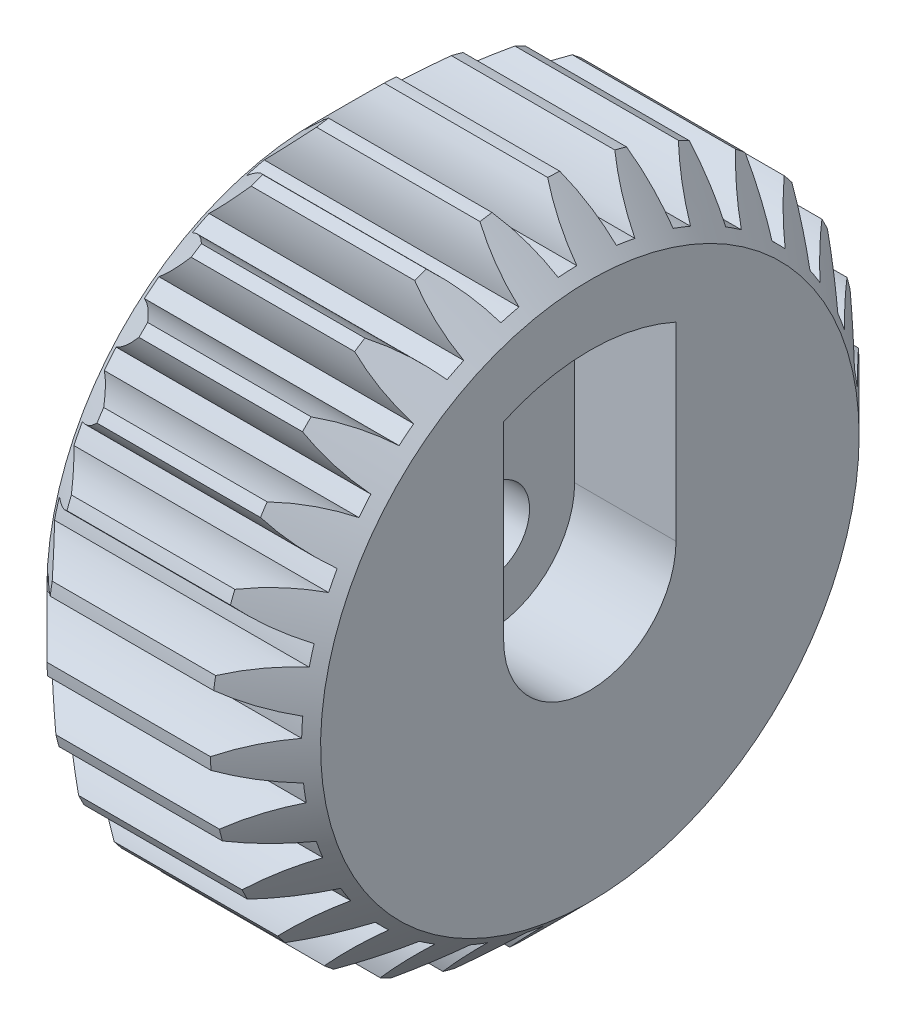
SolidWorks part; units mm, degrees
ref_plane "Plane1" through (0, 0, 0) normal (0, 0, 1) x (1, 0, 0)
ref_plane "Plane2" through (0, 0, 0) normal (0, 1, 0) x (1, 0, 0)
ref_plane "Plane3" through (0, 0, 0) normal (1, 0, 0) x (0, 0, -1)
sketch "HoldingSke" plane through (0, 0, 0) normal (0, 1, 0) x (1, 0, 0)
  line L0 (0, 0) -> (0.4698, -0.171)
  line L1 (-15, 0) -> (100, 0) construction
  line L2 (0, 0) -> (-2.1039, 2.3779)
  line L3 (0, 0) -> (-11.863, 4.5341)
  line L4 (0, 0) -> (8.1152, 2.9537)
  line L5 (0, 0) -> (-46.8476, -17.4728)
  line L6 (0, 0) -> (-39.7902, -26.8466)
  line L7 (-2.1039, 2.3779) -> (8.6589, 51.2074)
  line L8 (-76.2, 54.61) -> (-73.4, 54.61)
  line L9 (-71.009, 38.7566) -> (-53.1078, 45.2721)
  line L10 (-76.2, 71.12) -> (104.1128, 71.12)
  line L11 (0, 0) -> (-48, 0)
  line L12 (-76.2, 101.6) -> (-76.133, 101.6)
  line L13 (24.9733, 27.94) -> (52.9518, 28.4284)
  line L14 (24.9733, 27.94) -> (24.9743, 27.94)
  line L15 (24.9733, 27.94) -> (100.4006, 29.5858)
  line L16 (-63.627, -2) -> (-12.827, -2)
  circle A0 centre (0, 0) radius 10
  circle A1 centre (0, 0) radius 17.499
  circle A2 centre (0, 0) radius 37.5
  circle A3 centre (0, 0) radius 10
  dimension "MHD" = 34.998
  dimension "Hub_dia" = 75
  dimension "Bore" = 20
  dimension "MBD" = 20
  dimension "Num_teeth" = 20
  dimension "Pitch" = 0.5
  dimension "Overall_len" = 50
  dimension "Show_teeth" = 20
  dimension "Thickness" = 48
  dimension "OAL" = 50.0016
  dimension "T_dim" = 2.8
  dimension "Ap" = 20
  dimension "H" = 19.05
  dimension "Pitch_radius" = 180.3128
  dimension "Width" = 48
  dimension "Backlash" = 0.067
  dimension "Addendum_fac" = 1
  dimension "Dedendum_fac" = 1.25
  dimension "Clearance_fac" = 0.25
  dimension "Dedendum_add" = 0.001
  dimension "Module" = 2
sketch "BasProSke" plane through (0, 0, 0) normal (0, 1, 0) x (1, 0, 0)
  line L0 (-10, 0) -> (60, 0) construction
  line L1 (0, 0) -> (0, 22)
  line L2 (0, 0) -> (-31, 0)
  line L3 (-31, 0) -> (-31, 22)
  line L4 (-31, 22) -> (0, 22)
  dimension "Thickness" = 31
  dimension "Diameter" = 44
revolve "Base-Revolve" add sketch "BasProSke" angle 360 about L0
sketch "TooCutSke" plane through (0, 0, 0) normal (1, 0, 0) x (0, 0, -1)
  line L1 (0, 0) -> (0, 107) construction
  line L2 (0, 0) -> (-1.6864, 19.9288) construction
  line L3 (0, 0) -> (-6.2409, 39.4033) construction
  line L4 (-1.6864, 19.9288) -> (-3.1204, 19.7016) construction
  arc A0 (0.9862, 17.4712) -> (-0.9862, 17.4712) centre (0, 0) ccw
  arc A1 (2.9329, 21.8293) -> (-2.9329, 21.8293) centre (0, 0) ccw
  circle A2 centre (0, 0) radius 20 construction
  circle A3 centre (0, 0) radius 18.7939 construction
  arc A4 (-0.9862, 17.4712) -> (-2.9329, 21.8293) centre (-8.9313, 16.536) ccw
  arc A5 (2.9329, 21.8293) -> (0.9862, 17.4712) centre (8.9313, 16.536) ccw
  dimension "Root_dia" = 34.998
  dimension "Overcut_dia" = 44.0508
  dimension "Pitch_dia" = 40
  dimension "Base_dia" = 37.5877
  dimension "Flank_rad" = 8
  dimension "Half_ang" = 9
  dimension "Half_CT" = 1.4519
extrude "ToothCut" cut sketch "TooCutSke" against normal through all
fillet "Breaks" [suppressed] radius 0.04
fillet "RootFillets" [suppressed] radius 0.501
pattern_circular "TeethCuts" count 20 every 18 about axis through (-10, 0, 0) along (1, 0, 0) of "ToothCut"
sketch "HubNeaOneSke" plane through (0, 0, 0) normal (1, 0, 0) x (0, 0, -1)
  circle A0 centre (0, 0) radius 17.499
  dimension "Diameter" = 34.998
extrude "HubNearOne" [suppressed] add sketch "HubNeaOneSke" along normal blind 19.0016
sketch "HubNeaBotSke" plane through (0, 0, 0) normal (1, 0, 0) x (0, 0, -1)
  circle A0 centre (0, 0) radius 17.499
  dimension "Diameter" = 34.998
extrude "HubNearBoth" [suppressed] add sketch "HubNeaBotSke" along normal blind 9.5008
ref_plane "FarPln" through (31, 0, 0) normal (1, 0, 0) x (0, 0, -1)
sketch "HubFarSke" plane through (31, 0, 0) normal (1, 0, 0) x (0, 0, -1)
  circle A0 centre (0, 0) radius 17.499
  dimension "Diameter" = 34.998
extrude "HubFar" [suppressed] add sketch "HubFarSke" along normal blind 9.5008
sketch "BorSke" plane through (0, 0, 0) normal (1, 0, 0) x (0, 0, -1)
  circle A0 centre (0, 0) radius 10
  dimension "Diameter" = 20
extrude "Bore" cut sketch "BorSke" along normal mid plane 100.0033
sketch "KeySke" plane through (0, 0, 0) normal (1, 0, 0) x (0, 0, -1)
  line L0 (-3, 0) -> (-3, 12.8)
  line L1 (-3, 12.8) -> (3, 12.8)
  line L2 (3, 12.8) -> (3, 0)
  line L3 (0, 0) -> (0, 34) construction
  line L4 (-3, 0) -> (3, 0)
  dimension "Offset" = 12.8
  dimension "Width" = 6
extrude "Keyway" [suppressed] cut sketch "KeySke" along normal mid plane 100.0033
pattern_circular "Keyway2" [suppressed] count 2 every 90 about axis through (-10, 0, 0) along (1, 0, 0)
sketch "Sketch1" plane through (0, 0, 0) normal (0, 0, 1) x (1, 0, 0)
  line L0 (-15.5, 21.6391) -> (-15.5, 38.001) construction
  line L1 (-31, 21.6391) -> (0, 21.6391) construction
  line L2 (0, 14.6563) -> (0, 0) construction
  line L3 (0, -0.9862) -> (0, 0.9862) construction
  line L4 (0, 14.6563) -> (-8.8638, 23.5201) construction
  line L5 (0, 21.8063) -> (0, 14.6563) construction
  line L6 (-31, 21.8063) -> (-31, 21.6391)
  line L7 (-31, 21.6391) -> (0, 21.6391)
  line L8 (0, 21.6391) -> (0, 21.8063)
  line L9 (0, 21.8063) -> (-31, 21.8063)
  line L10 (-31, 21.8063) -> (-31, 21.6391) construction
  line L11 (-31, 21.6391) -> (-15.5, 21.6391) construction
  line L13 (-7.15, 21.8063) -> (-31, 21.8063) construction
  line L14 (0, 21.8063) -> (-7.15, 21.8063) construction
  line L16 (-7.15, 28.8196) -> (7.9018, 28.8196) construction
  line L17 (7.9018, 28.8196) -> (7.9018, 14.6563) construction
  line L18 (7.9018, 14.6563) -> (0, 14.6563) construction
  line L19 (0, 0) -> (16.2139, 0) construction
  line L20 (-31, 21.8063) -> (-23.85, 21.8063) construction
  line L21 (-31, 21.8063) -> (-31, 14.6563) construction
  line L22 (-38.9018, 14.6563) -> (-31, 14.6563) construction
  line L23 (-38.9018, 28.8196) -> (-38.9018, 14.6563) construction
  line L24 (-23.85, 28.8196) -> (-38.9018, 28.8196) construction
  line L25 (-23.85, 21.8063) -> (-23.85, 28.8196) construction
  line L26 (-31, 14.6563) -> (-23.85, 21.8063) construction
  line L27 (-34.2364, 10.8543) -> (-21.7624, 23.3283)
  line L28 (-23.45, 21.6406) -> (-23.45, 21.8063)
  line L29 (-23.45, 29.2196) -> (-39.3018, 29.2196)
  line L30 (-39.3018, 29.2196) -> (-39.3018, 14.2563)
  line L32 (-30.8343, 14.2563) -> (-23.45, 21.6406) construction
  line L33 (-23.45, 29.2196) -> (-21.7624, 23.3283)
  line L34 (-23.45, 21.6406) -> (-23.45, 29.2196) construction
  line L35 (-8.8638, 23.5201) -> (-7.15, 28.8196) construction
  line L37 (-9.3197, 23.4103) -> (-7.441, 29.2196)
  line L38 (-7.441, 29.2196) -> (8.3018, 29.2196)
  line L39 (8.3018, 29.2196) -> (8.3018, 14.2563)
  line L40 (0, 14.2563) -> (-0.1657, 14.2563)
  line L41 (2.7695, 11.3212) -> (-9.3197, 23.4103)
  line L45 (-0.1657, 14.2563) -> (-9.3197, 23.4103) construction
  line L46 (8.3018, 14.2563) -> (-0.1657, 14.2563) construction
  line L47 (2.7695, 11.3212) -> (8.3018, 14.2563)
  line L48 (-34.2364, 10.8543) -> (-39.3018, 14.2563)
  line L49 (-39.3018, 14.2563) -> (-30.8343, 14.2563) construction
  dimension "D2" = 7.15
  dimension "D3" = 0.4
  dimension "D4" = 0.4
revolve "Cut-Revolve1" cut sketch "Sketch1" angle 360 about L19
sketch "Sketch3" plane through (2.7668, 0, 0) normal (-1, 0, 0) x (0, 0, 1)
  circle A121 centre (42.3703, 91.3357) radius 10
  arc A240 (36.3122, 64.5123) -> (36.9681, 59.795) centre (48.2894, 63.7733) ccw
  arc A241 (36.9681, 59.795) -> (38.1586, 59.614) centre (42.3703, 91.3357) ccw
  arc A242 (38.1586, 59.614) -> (40.1863, 63.9235) centre (28.5303, 66.7761) ccw
  arc A243 (40.1863, 63.9235) -> (42.0215, 63.8389) centre (42.3703, 91.3357) ccw
  arc A244 (42.0215, 63.8389) -> (43.6438, 59.361) centre (53.8906, 65.6062) ccw
  arc A245 (43.6438, 59.361) -> (44.846, 59.4316) centre (42.3703, 91.3357) ccw
  arc A246 (44.846, 59.4316) -> (45.9333, 64.0685) centre (33.9389, 64.4353) ccw
  arc A247 (45.9333, 64.0685) -> (47.746, 64.3672) centre (42.3703, 91.3357) ccw
  arc A248 (47.746, 64.3672) -> (50.2639, 60.3245) centre (58.9883, 68.5637) ccw
  arc A249 (50.2639, 60.3245) -> (51.4251, 60.6435) centre (42.3703, 91.3357) ccw
  arc A250 (51.4251, 60.6435) -> (51.5247, 65.4051) centre (39.7161, 63.2701) ccw
  arc A251 (51.5247, 65.4051) -> (53.2356, 66.0742) centre (42.3703, 91.3357) ccw
  arc A252 (53.2356, 66.0742) -> (56.539, 62.6433) centre (63.3597, 72.5164) ccw
  arc A253 (56.539, 62.6433) -> (57.6085, 63.1968) centre (42.3703, 91.3357) ccw
  arc A254 (57.6085, 63.1968) -> (56.7159, 67.8751) centre (45.6093, 63.3316) ccw
  arc A255 (56.7159, 67.8751) -> (58.2503, 68.8852) centre (42.3703, 91.3357) ccw
  arc A256 (58.2503, 68.8852) -> (62.1948, 66.2162) centre (66.8138, 77.2916) ccw
  arc A257 (62.1948, 66.2162) -> (63.1259, 66.9799) centre (42.3703, 91.3357) ccw
  arc A258 (63.1259, 66.9799) -> (61.2801, 71.3703) centre (51.3609, 64.6169) ccw
  arc A259 (61.2801, 71.3703) -> (62.571, 72.6775) centre (42.3703, 91.3357) ccw
  arc A260 (62.571, 72.6775) -> (66.9842, 70.8868) centre (69.1996, 82.6806) ccw
  arc A261 (66.9842, 70.8868) -> (67.7362, 71.8274) centre (42.3703, 91.3357) ccw
  arc A262 (67.7362, 71.8274) -> (65.0179, 75.7382) centre (56.7195, 67.0701) ccw
  arc A263 (65.0179, 75.7382) -> (66.0088, 77.2852) centre (42.3703, 91.3357) ccw
  arc A264 (66.0088, 77.2852) -> (70.6979, 76.4512) centre (70.4128, 88.4478) ccw
  arc A265 (70.6979, 76.4512) -> (71.2379, 77.5276) centre (42.3703, 91.3357) ccw
  arc A266 (71.2379, 77.5276) -> (67.7659, 80.7877) centre (61.4511, 70.5837) ccw
  arc A267 (67.7659, 80.7877) -> (68.4135, 82.5069) centre (42.3703, 91.3357) ccw
  arc A268 (68.4135, 82.5069) -> (73.1736, 82.6661) centre (70.4004, 94.3413) ccw
  arc A269 (73.1736, 82.6661) -> (73.4779, 83.8312) centre (42.3703, 91.3357) ccw
  arc A270 (73.4779, 83.8312) -> (69.404, 86.2983) centre (65.3487, 75.0043) ccw
  arc A271 (69.404, 86.2983) -> (69.68, 88.1145) centre (42.3703, 91.3357) ccw
  arc A272 (69.68, 88.1145) -> (74.3029, 89.2599) centre (69.163, 100.1034) ccw
  arc A273 (74.3029, 89.2599) -> (74.3584, 90.4629) centre (42.3703, 91.3357) ccw
  arc A274 (74.3584, 90.4629) -> (69.8606, 92.029) centre (68.2421, 80.1386) ccw
  arc A275 (69.8606, 92.029) -> (69.753, 93.8629) centre (42.3703, 91.3357) ccw
  arc A276 (69.753, 93.8629) -> (74.0367, 95.9444) centre (66.7546, 105.4823) ccw
  arc A277 (74.0367, 95.9444) -> (73.8409, 97.1326) centre (42.3703, 91.3357) ccw
  arc A278 (73.8409, 97.1326) -> (69.1157, 97.7294) centre (70.0047, 85.7623) ccw
  arc A279 (69.1157, 97.7294) -> (68.6291, 99.5009) centre (42.3703, 91.3357) ccw
  arc A280 (68.6291, 99.5009) -> (72.3865, 102.4275) centre (63.2805, 110.2429) ccw
  arc A281 (72.3865, 102.4275) -> (71.9479, 103.5491) centre (42.3703, 91.3357) ccw
  arc A282 (71.9479, 103.5491) -> (67.2019, 103.1503) centre (70.5596, 91.6296) ccw
  arc A283 (67.2019, 103.1503) -> (66.3577, 104.7819) centre (42.3703, 91.3357) ccw
  arc A284 (66.3577, 104.7819) -> (69.4245, 108.4258) centre (58.8925, 114.1772) ccw
  arc A285 (69.4245, 108.4258) -> (68.7623, 109.4317) centre (42.3703, 91.3357) ccw
  arc A286 (68.7623, 109.4317) -> (64.2029, 108.0549) centre (69.8825, 97.4841) ccw
  arc A287 (64.2029, 108.0549) -> (63.0379, 109.4754) centre (42.3703, 91.3357) ccw
  arc A288 (63.0379, 109.4754) -> (65.28, 113.6773) centre (53.7825, 117.1133) ccw
  arc A289 (65.28, 113.6773) -> (64.4232, 114.5234) centre (42.3703, 91.3357) ccw
  arc A290 (64.4232, 114.5234) -> (60.2497, 112.2288) centre (68.0029, 103.0698) ccw
  arc A291 (60.2497, 112.2288) -> (58.8148, 113.376) centre (42.3703, 91.3357) ccw
  arc A292 (58.8148, 113.376) -> (60.1343, 117.9522) centre (48.1736, 118.9227) ccw
  arc A293 (60.1343, 117.9522) -> (59.1203, 118.6018) centre (42.3703, 91.3357) ccw
  arc A294 (59.1203, 118.6018) -> (55.515, 115.4896) centre (65.0031, 108.1427) ccw
  arc A295 (55.515, 115.4896) -> (53.873, 116.3133) centre (42.3703, 91.3357) ccw
  arc A296 (53.873, 116.3133) -> (54.2122, 121.0639) centre (42.3111, 119.5264) ccw
  arc A297 (54.2122, 121.0639) -> (53.0853, 121.4884) centre (42.3703, 91.3357) ccw
  arc A298 (53.0853, 121.4884) -> (50.2059, 117.6947) centre (61.0142, 112.4811) ccw
  arc A299 (50.2059, 117.6947) -> (48.4285, 118.1591) centre (42.3703, 91.3357) ccw
  arc A300 (48.4285, 118.1591) -> (47.7726, 122.8764) centre (36.4513, 118.898) ccw
  arc A301 (47.7726, 122.8764) -> (46.582, 123.0573) centre (42.3703, 91.3357) ccw
  arc A302 (46.582, 123.0573) -> (44.5543, 118.7478) centre (56.2104, 115.8953) ccw
  arc A303 (44.5543, 118.7478) -> (42.7192, 118.8325) centre (42.3703, 91.3357) ccw
  arc A304 (42.7192, 118.8325) -> (41.0969, 123.3103) centre (30.8501, 117.0651) ccw
  arc A305 (41.0969, 123.3103) -> (39.8947, 123.2398) centre (42.3703, 91.3357) ccw
  arc A306 (39.8947, 123.2398) -> (38.8073, 118.6029) centre (50.8017, 118.2361) ccw
  arc A307 (38.8073, 118.6029) -> (36.9947, 118.3041) centre (42.3703, 91.3357) ccw
  arc A308 (36.9947, 118.3041) -> (34.4768, 122.3468) centre (25.7524, 114.1077) ccw
  arc A309 (34.4768, 122.3468) -> (33.3156, 122.0279) centre (42.3703, 91.3357) ccw
  arc A310 (33.3156, 122.0279) -> (33.216, 117.2662) centre (45.0246, 119.4012) ccw
  arc A311 (33.216, 117.2662) -> (31.5051, 116.5971) centre (42.3703, 91.3357) ccw
  arc A312 (31.5051, 116.5971) -> (28.2017, 120.028) centre (21.3809, 110.155) ccw
  arc A313 (28.2017, 120.028) -> (27.1322, 119.4746) centre (42.3703, 91.3357) ccw
  arc A314 (27.1322, 119.4746) -> (28.0248, 114.7963) centre (39.1314, 119.3398) ccw
  arc A315 (28.0248, 114.7963) -> (26.4904, 113.7861) centre (42.3703, 91.3357) ccw
  arc A316 (26.4904, 113.7861) -> (22.5459, 116.4552) centre (17.9269, 105.3798) ccw
  arc A317 (22.5459, 116.4552) -> (21.6147, 115.6915) centre (42.3703, 91.3357) ccw
  arc A318 (21.6147, 115.6915) -> (23.4605, 111.301) centre (33.3798, 118.0544) ccw
  arc A319 (23.4605, 111.301) -> (22.1697, 109.9939) centre (42.3703, 91.3357) ccw
  arc A320 (22.1697, 109.9939) -> (17.7564, 111.7845) centre (15.5411, 99.9908) ccw
  arc A321 (17.7564, 111.7845) -> (17.0044, 110.8439) centre (42.3703, 91.3357) ccw
  arc A322 (17.0044, 110.8439) -> (19.7227, 106.9332) centre (28.0211, 115.6013) ccw
  arc A323 (19.7227, 106.9332) -> (18.7318, 105.3862) centre (42.3703, 91.3357) ccw
  arc A324 (18.7318, 105.3862) -> (14.0427, 106.2202) centre (14.3279, 94.2235) ccw
  arc A325 (14.0427, 106.2202) -> (13.5028, 105.1438) centre (42.3703, 91.3357) ccw
  arc A326 (13.5028, 105.1438) -> (16.9747, 101.8836) centre (23.2896, 112.0877) ccw
  arc A327 (16.9747, 101.8836) -> (16.3271, 100.1644) centre (42.3703, 91.3357) ccw
  arc A328 (16.3271, 100.1644) -> (11.5671, 100.0053) centre (14.3402, 88.3301) ccw
  arc A329 (11.5671, 100.0053) -> (11.2627, 98.8401) centre (42.3703, 91.3357) ccw
  arc A330 (11.2627, 98.8401) -> (15.3367, 96.3731) centre (19.392, 107.6671) ccw
  arc A331 (15.3367, 96.3731) -> (15.0606, 94.5568) centre (42.3703, 91.3357) ccw
  arc A332 (15.0606, 94.5568) -> (10.4377, 93.4115) centre (15.5777, 82.568) ccw
  arc A333 (10.4377, 93.4115) -> (10.3822, 92.2085) centre (42.3703, 91.3357) ccw
  arc A334 (10.3822, 92.2085) -> (14.8801, 90.6424) centre (16.4986, 102.5327) ccw
  arc A335 (14.8801, 90.6424) -> (14.9877, 88.8084) centre (42.3703, 91.3357) ccw
  arc A336 (14.9877, 88.8084) -> (10.704, 86.7269) centre (17.986, 77.1891) ccw
  arc A337 (10.704, 86.7269) -> (10.8998, 85.5387) centre (42.3703, 91.3357) ccw
  arc A338 (10.8998, 85.5387) -> (15.6249, 84.942) centre (14.736, 96.909) ccw
  arc A339 (15.6249, 84.942) -> (16.1115, 83.1705) centre (42.3703, 91.3357) ccw
  arc A340 (16.1115, 83.1705) -> (12.3542, 80.2438) centre (21.4602, 72.4284) ccw
  arc A341 (12.3542, 80.2438) -> (12.7927, 79.1223) centre (42.3703, 91.3357) ccw
  arc A342 (12.7927, 79.1223) -> (17.5387, 79.521) centre (14.1811, 91.0417) ccw
  arc A343 (17.5387, 79.521) -> (18.383, 77.8894) centre (42.3703, 91.3357) ccw
  arc A344 (18.383, 77.8894) -> (15.3162, 74.2455) centre (25.8481, 68.4941) ccw
  arc A345 (15.3162, 74.2455) -> (15.9784, 73.2397) centre (42.3703, 91.3357) ccw
  arc A346 (15.9784, 73.2397) -> (20.5378, 74.6164) centre (14.8582, 85.1873) ccw
  arc A347 (20.5378, 74.6164) -> (21.7028, 73.196) centre (42.3703, 91.3357) ccw
  arc A348 (21.7028, 73.196) -> (19.4606, 68.9941) centre (30.9582, 65.5581) ccw
  arc A349 (19.4606, 68.9941) -> (20.3175, 68.1479) centre (42.3703, 91.3357) ccw
  arc A350 (20.3175, 68.1479) -> (24.491, 70.4425) centre (16.7377, 79.6015) ccw
  arc A351 (24.491, 70.4425) -> (25.9259, 69.2954) centre (42.3703, 91.3357) ccw
  arc A352 (25.9259, 69.2954) -> (24.6064, 64.7191) centre (36.567, 63.7487) ccw
  arc A353 (24.6064, 64.7191) -> (25.6204, 64.0696) centre (42.3703, 91.3357) ccw
  arc A354 (25.6204, 64.0696) -> (29.2256, 67.1818) centre (19.7375, 74.5286) ccw
  arc A355 (29.2256, 67.1818) -> (30.8677, 66.358) centre (42.3703, 91.3357) ccw
  arc A356 (30.8677, 66.358) -> (30.5284, 61.6074) centre (42.4295, 63.145) ccw
  arc A357 (30.5284, 61.6074) -> (31.6554, 61.1829) centre (42.3703, 91.3357) ccw
  arc A358 (31.6554, 61.1829) -> (34.5347, 64.9766) centre (23.7265, 70.1903) ccw
  arc A359 (34.5347, 64.9766) -> (36.3122, 64.5123) centre (42.3703, 91.3357) ccw
extrude "Boss-Extrude2" add sketch "Sketch3" along normal blind 31 separate body
sketch "Sketch4" plane through (-28.2332, 0, 0) normal (-1, 0, 0) x (0, 0, 1)
  line L0 (74.3363, 89.8611) -> (10.4043, 92.8102) construction
  arc A0 (74.3029, 89.2599) -> (74.3584, 90.4629) centre (42.3703, 91.3357) ccw construction
  arc A1 (10.4377, 93.4115) -> (10.3822, 92.2085) centre (42.3703, 91.3357) ccw construction
ref_plane "Plane4" through (0, 93.0921, 4.2942) normal (0, 0.9989, 0.0461) x (0, 0.0461, -0.9989)
sketch "Sketch5" plane through (0, 93.0921, 4.2942) normal (0, 0.9989, 0.0461) x (0, 0.0461, -0.9989)
  line L0 (-73.0602, 18.1339) -> (-60.2835, 30.9105) construction
  line L1 (-60.2835, 30.9105) -> (-73.0602, 30.9105) construction
  line L2 (-73.0602, 30.9105) -> (-73.0602, 18.1339) construction
  line L3 (-70.1109, 28.2332) -> (-62.9609, 28.2332) construction
  line L4 (-70.1109, 28.2332) -> (-70.1109, 21.0832) construction
  line L5 (-70.1109, -2.7668) -> (-6.1223, -2.7668) construction
  line L6 (-70.1109, 28.2332) -> (-70.1109, -2.7668) construction
  line L7 (-38.1166, -2.7668) -> (-38.1166, -25.5624) construction
  line L8 (-70.1109, 12.7332) -> (-78.3161, 12.7332) construction
  line L9 (-73.2602, 31.1105) -> (-73.2602, 17.6511)
  line L10 (-73.2602, 17.6511) -> (-59.8007, 31.1105)
  line L11 (-59.8007, 31.1105) -> (-73.2602, 31.1105)
  line L12 (-70.1109, -2.7668) -> (-70.1109, 4.3832) construction
  line L13 (-70.1109, -2.7668) -> (-62.9609, -2.7668) construction
  line L14 (-73.0602, -5.4442) -> (-73.0602, 7.3324) construction
  line L15 (-60.2835, -5.4442) -> (-73.0602, -5.4442) construction
  line L16 (-73.0602, 7.3324) -> (-60.2835, -5.4442) construction
  line L17 (-59.8007, -5.6442) -> (-73.2602, -5.6442)
  line L18 (-73.2602, 7.8152) -> (-59.8007, -5.6442)
  line L19 (-73.2602, -5.6442) -> (-73.2602, 7.8152)
  dimension "D1" = 7.15
  dimension "D2" = 0.2
revolve "Cut-Revolve2" cut sketch "Sketch5" angle 360 about L7
delete or keep bodies "Body-Delete/Keep 1" type delete bodies bodies 105
sketch "Sketch6" plane through (-28.2332, 0, 0) normal (-1, 0, 0) x (0, 0, 1)
  circle A0 centre (42.3703, 91.3357) radius 10 construction
  circle A1 centre (42.3703, 91.3357) radius 10
  circle A2 centre (42.3703, 91.3357) radius 4.05
  dimension "D1" = 8.1
extrude "Boss-Extrude3" add sketch "Sketch6" against normal up to surface (31 mm away) up to face at (2.7668, 91.3357, 52.3703)
chamfer "Chamfer1" distance 1 angle 45 2 edges at (2.7668, 91.3357, 46.4203) (-28.2332, 91.3357, 46.4203)
ref_plane "Plane5" through (-12.7332, 0, 0) normal (1, 0, 0) x (0, 0, -1)
sketch "Sketch7" plane through (2.7668, 0, 0) normal (1, 0, 0) x (0, 0, -1)
  line L0 (-42.3703, 91.3357) -> (-19.5336, 91.3357) construction
  line L3 (-50.8703, 91.3357) -> (-50.8703, 110.058)
  line L4 (-33.8703, 91.3357) -> (-33.8703, 110.058)
  arc A0 (-50.8703, 91.3357) -> (-33.8703, 91.3357) centre (-42.3703, 91.3357) ccw
  arc A1 (-33.8703, 110.058) -> (-50.8703, 110.058) centre (-42.3703, 91.3357) ccw
  circle A2 centre (-42.3703, 91.3357) radius 24.5615
  circle A3 centre (-42.3703, 91.3357) radius 24.5615 construction
  circle A4 centre (-42.3703, 91.3357) radius 20.5615 construction
  dimension "D2" = 17
  dimension "D1" = 0
  dimension "D3" = 4
extrude "Cut-Extrude1" cut sketch "Sketch7" against normal blind 12
sketch "Sketch8" plane through (2.7668, 0, 0) normal (1, 0, 0) x (0, 0, -1)
  circle A0 centre (-42.3703, 91.3357) radius 24.5615 construction
  circle A1 centre (-42.3703, 91.3357) radius 24.5615 construction
  circle A2 centre (-42.3703, 91.3357) radius 34.5615
  dimension "D1" = 10
extrude "Cut-Extrude2" cut sketch "Sketch8" against normal blind 2
mirror "Mirror1" about plane through (-12.7332, 0, 0) normal (1, 0, 0) of "Cut-Extrude2", "Cut-Extrude1"
equation "' \"Module@HoldingSke\" = 6.35"
equation "' \"Num_teeth@HoldingSke\" = 12"
equation "' \"Ap@HoldingSke\" =  20"
equation "' \"Ap@HoldingSke\" = 20"
equation "' \"Width@HoldingSke\" = 0.5 * 25.4"
equation "' \"Hub_dia@HoldingSke\"= 1 * 25.4"
equation "' \"Hub_dia@HoldingSke\" = 1 * 25.4"
equation "' \"Overall_len@HoldingSke\" = 1.0 * 25.4"
equation "' \"Bore@HoldingSke\" = 0.75 * 25.4"
equation "' \"T_dim@HoldingSke\" = 0.1 * 25.4"
equation "' \"Width@KeySke\" = 0.25 * 25.4"
equation "' \"Show_teeth@HoldingSke\" = 13"
equation "' \"Backlash@HoldingSke\" = 0.009 * 25.4"
equation "' \"Addendum_fac@HoldingSke\" = 1.0"
equation "' \"Dedendum_fac@HoldingSke\" = 1.25"
equation "' \"Dedendum_add@HoldingSke\" = 0.00005 * 25.4"
equation "' \"Clearance_fac@HoldingSke\" = 0.25"
equation "\"Pitch@HoldingSke\" = 1 / \"Module@HoldingSke\""
equation "\"Overcut_dia@TooCutSke\" = (\"Num_teeth@HoldingSke\" + 2 * \"Addendum_fac@HoldingSke\") / \"Pitch@HoldingSke\" + 0.002 * 25.4"
equation "\"Pitch_dia@TooCutSke\" = \"Num_teeth@HoldingSke\" / \"Pitch@HoldingSke\""
equation "\"Base_dia@TooCutSke\" = \"Num_teeth@HoldingSke\" / \"Pitch@HoldingSke\" * cos((\"Ap@HoldingSke\"  * 3.14159265 / 180))"
equation "\"Root_dia@TooCutSke\" = (\"Num_teeth@HoldingSke\" + 2) / \"Pitch@HoldingSke\" - 2 * (\"Addendum_fac@HoldingSke\" + \"Dedendum_fac@HoldingSke\") / \"Pitch@HoldingSke\" - \"Dedendum_add@HoldingSke\" * 2"
equation "\"Half_ang@TooCutSke\" = 180 / \"Num_teeth@HoldingSke\""
equation "\"Half_CT@TooCutSke\" = \"Num_teeth@HoldingSke\" / \"Pitch@HoldingSke\" * sin((3.14159265 / 2 / \"Num_teeth@HoldingSke\")) / 2 - 7 * \"Backlash@HoldingSke\" / 4"
equation "\"Flank_rad@TooCutSke\" = \"Num_teeth@HoldingSke\" / \"Pitch@HoldingSke\" / 5"
equation "\"Radius@RootFillets\" = \"Clearance_fac@HoldingSke\" / \"Pitch@HoldingSke\" + \"Dedendum_add@HoldingSke\""
equation "\"Break_rad@Breaks\" = 0.02 / \"Pitch@HoldingSke\""
equation "\"Thickness@HoldingSke\" = \"Width@HoldingSke\""
equation "\"OAL@HoldingSke\" = \"Thickness@HoldingSke\""
equation "\"MHD@HoldingSke\" = (\"Num_teeth@HoldingSke\" + 2) / \"Pitch@HoldingSke\" - 2 * (\"Addendum_fac@HoldingSke\" + \"Dedendum_fac@HoldingSke\")  / \"Pitch@HoldingSke\" - \"Dedendum_add@HoldingSke\" * 2"
equation "\"MBD@HoldingSke\" = (\"Num_teeth@HoldingSke\" + 2) / \"Pitch@HoldingSke\" - 2 * (\"Addendum_fac@HoldingSke\" + \"Dedendum_fac@HoldingSke\")  / \"Pitch@HoldingSke\" - \"Dedendum_add@HoldingSke\" * 2 - 0.002 * 25.4"
equation "\"MHD@HoldingSke\" = ((sgn( \"MHD@HoldingSke\" - \"Hub_dia@HoldingSke\" )-1)*( \"MHD@HoldingSke\" - \"Hub_dia@HoldingSke\" ))/-2+ \"Hub_dia@HoldingSke\""
equation "\"MBD@HoldingSke\" = ((sgn( \"MBD@HoldingSke\" - \"Bore@HoldingSke\" )-1)*( \"MBD@HoldingSke\" - \"Bore@HoldingSke\" ))/-2+ \"Bore@HoldingSke\""
equation "\"OAL@HoldingSke\" = ((sgn( \"OAL@HoldingSke\" - \"Overall_len@HoldingSke\" )+1)*( \"OAL@HoldingSke\" - \"Overall_len@HoldingSke\" ))/2 + \"Overall_len@HoldingSke\" + 0.000002 * 25.4"
equation "\"Num_teeth@TeethCuts\" = int( \"Show_teeth@HoldingSke\" ) + 1"
equation "\"Num_teeth@TeethCuts\" = ((sgn( \"Num_teeth@TeethCuts\" - \"Num_teeth@HoldingSke\" )-1)*( \"Num_teeth@TeethCuts\" - \"Num_teeth@HoldingSke\" ))/-2+ \"Num_teeth@HoldingSke\""
equation "\"Num_teeth@TeethCuts\" = ((sgn( \"Num_teeth@TeethCuts\" - 2.0)+1)*( \"Num_teeth@TeethCuts\" - 2.0))/2 +2.0"
equation "\"Angle@TeethCuts\" = 360.0 / \"Num_teeth@HoldingSke\""
equation "\"Diameter@BasProSke\" = (\"Num_teeth@HoldingSke\" + 2 * \"Addendum_fac@HoldingSke\") / \"Pitch@HoldingSke\""
equation "\"Thickness@BasProSke\" = \"fullThickness@gearedShaftAttachment<3>.Part\" - 2 * \"wallThickness@gearedShaftAttachment<3>.Part\" - 4"
equation "' \"Fillet_rad@BasProSke\" =  \"Thickness@HoldingSke\" * 0.05"
equation "' \"Fillet_rad@BasProSke\" = \"Thickness@HoldingSke\" * 0.05"
equation "\"MHD@HoldingSke\" = ((sgn( \"MHD@HoldingSke\" - \"Root_dia@TooCutSke\" )-1)*( \"MHD@HoldingSke\" - \"Root_dia@TooCutSke\" ))/-2+ \"Root_dia@TooCutSke\""
equation "\"Diameter@HubNeaOneSke\" = \"MHD@HoldingSke\""
equation "\"Length@HubNearOne\" = \"OAL@HoldingSke\" - \"Thickness@BasProSke\""
equation "\"Diameter@HubNeaBotSke\" = \"MHD@HoldingSke\""
equation "\"Length@HubNearBoth\" = ( \"OAL@HoldingSke\" - \"Thickness@BasProSke\" ) / 2.0"
equation "\"Thickness@FarPln\" = \"Thickness@BasProSke\""
equation "\"Diameter@HubFarSke\" = \"MHD@HoldingSke\""
equation "\"Length@HubFar\" = ( \"OAL@HoldingSke\" - \"Thickness@BasProSke\" ) / 2.0"
equation "\"Diameter@BorSke\" = \"MBD@HoldingSke\""
equation "\"D1@Bore\" = \"OAL@HoldingSke\" * 2.0"
equation "\"D1@Keyway\" = \"OAL@HoldingSke\" * 2.0"
equation "\"Offset@KeySke\" = \"T_dim@HoldingSke\" + \"MBD@HoldingSke\" / 2.0"
equation "\"D2@Sketch1\" = \"wallThickness@gearedShaftAttachment<3>.Part\" - 2.85"
equation "\"D4@Sketch1\"=\"D3@Sketch1\""
equation "\"D1@Boss-Extrude2\" = \"fullThickness@gearedShaftAttachment<3>.Part\" - 2 * \"wallThickness@gearedShaftAttachment<3>.Part\" - 4"
equation "\"D1@Sketch5\" = \"wallThickness@gearedShaftAttachment<3>.Part\" - 2.85"
